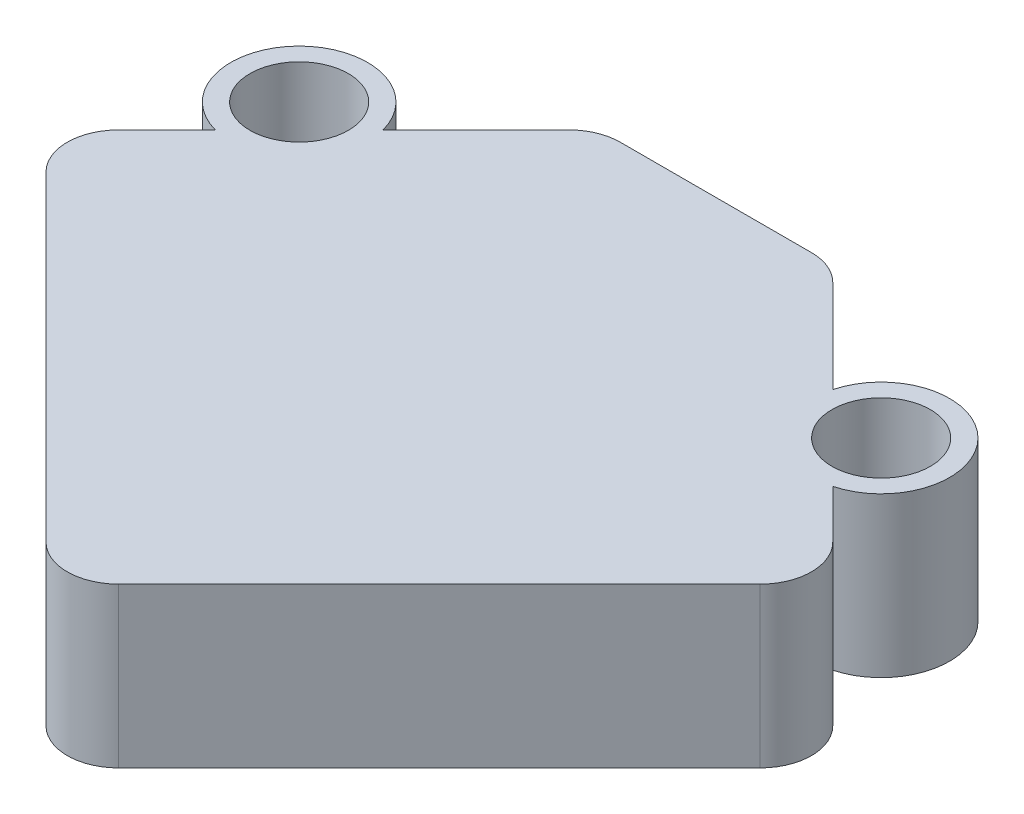
SolidWorks part; units mm, degrees
ref_plane "Front Plane" through (0, 0, 0) normal (0, 0, 1) x (1, 0, 0)
ref_plane "Top Plane" through (0, 0, 0) normal (0, 1, 0) x (1, 0, 0)
ref_plane "Right Plane" through (0, 0, 0) normal (1, 0, 0) x (0, 0, -1)
sketch "Sketch1" plane through (0, 0, 0) normal (0, 1, 0) x (1, 0, 0)
  line L0 (-38.2767, 0) -> (40.0394, 0) construction
  line L1 (0, 59.0518) -> (0, -52.7563) construction
  line L2 (0, 0) -> (52.4416, -52.4416) construction
  line L3 (-20.1525, 0) -> (0, -20.1525)
  line L4 (-20.1525, 0) -> (0, 20.1525)
  line L5 (0, -20.1525) -> (20.1525, 0)
  line L6 (0, 20.1525) -> (20.1525, 0)
  line L7 (-20.1525, 0) -> (20.1525, 0) construction
  line L8 (0, -20.1525) -> (0, 20.1525) construction
  line L9 (-22.981, 0) -> (0, -22.981)
  line L10 (0, -22.981) -> (22.981, 0)
  line L11 (0, 31.4663) -> (-27.2236, 4.2426)
  line L12 (-22.981, 0) -> (-27.2236, 4.2426)
  line L13 (0, 31.4663) -> (27.2236, 4.2426)
  line L14 (22.981, 0) -> (27.2236, 4.2426)
  line L15 (-22.981, 0) -> (0, 22.981)
  line L16 (0, 22.981) -> (22.981, 0)
  line L17 (-17, 8.8094) -> (2.8284, 28.6378) construction
  line L18 (-13.6118, 17.8544) -> (-7.955, 12.1976) construction
  line L19 (-10.7834, 15.026) -> (2.8284, 28.6378) construction
  circle A0 centre (-17, 8.8094) radius 1.75
  circle A1 centre (17, 8.8094) radius 1.75
  circle A2 centre (-17, 8.8094) radius 4
  circle A3 centre (17, 8.8094) radius 4
  point P8 (0, 0)
  dimension "D5" = 3.5
  dimension "D1" = 45
  dimension "D2" = 28.5
  dimension "D3" = 2
  dimension "D4" = 8
  dimension "D6" = 34
extrude "Boss-Extrude1" add sketch "Sketch1" along normal blind 7 contours L16 A3 L6 L5 L3 L4 A2 L15 L9 L10 | L6 A3 L16 L15 A2 L4 | A3 L16 A1 | L15 A2 A0 | A2 L15 | A3 L16 region at (-10.4604, 0, 10.4604) region at (-13.2739, 0, -7.266) region at (-15.0059, 0, -6.8153) region at (-20.7563, 0, -7.8029) region at (15.0059, 0, -6.8153) region at (15.9935, 0, -12.5657)
sketch "Sketch2" plane through (0, 7, 0) normal (0, 1, 0) x (1, 0, 0)
  circle A0 centre (-17, 8.8094) radius 2.875
  circle A1 centre (17, 8.8094) radius 2.875
  dimension "D1" = 5.75
extrude "Cut-Extrude1" cut sketch "Sketch2" against normal offset from surface (5 mm away) 2 up to face at (0, 0, -4.7583)
sketch "Sketch4" plane through (0, 7, 0) normal (0, 1, 0) x (1, 0, 0)
  line L0 (-22.981, 0) -> (22.981, 0) construction
  line L1 (-4, 16.1525) -> (4, 16.1525) construction
  line L2 (-20.1525, 0) -> (0, 20.1525) construction
  line L3 (0, 20.1525) -> (20.1525, 0) construction
  line L4 (-13.1363, 9.8447) -> (0, 22.981) construction
  line L5 (-6.8284, 16.1525) -> (6.8284, 16.1525)
  line L6 (-6.8284, 16.1525) -> (-6.8284, 22.981)
  line L7 (-6.8284, 22.981) -> (6.8284, 22.981)
  line L8 (6.8284, 16.1525) -> (6.8284, 22.981)
  line L9 (0, 22.981) -> (13.1363, 9.8447) construction
  dimension "D1" = 8
extrude "Cut-Extrude3" cut sketch "Sketch4" against normal up to next
sketch "Sketch5" plane through (0, 7, 0) normal (0, 1, 0) x (1, 0, 0)
  line L0 (-4, 16.1525) -> (4, 16.1525)
  line L12 (6.8284, 16.1525) -> (4, 16.1525)
  line L13 (4, 16.1525) -> (20.1525, 0)
  line L14 (20.1525, 0) -> (0, -20.1525)
  line L15 (0, -20.1525) -> (-20.1525, 0)
  line L16 (-20.1525, 0) -> (-4, 16.1525)
  line L17 (-4, 16.1525) -> (-6.8284, 16.1525)
  line L18 (-6.8284, 16.1525) -> (-13.1363, 9.8447)
  line L19 (-18.0353, 4.9457) -> (-22.981, 0)
  line L20 (-22.981, 0) -> (0, -22.981)
  line L21 (0, -22.981) -> (22.981, 0)
  line L22 (22.981, 0) -> (18.0353, 4.9457)
  line L23 (13.1363, 9.8447) -> (6.8284, 16.1525)
  line L24 (6.8284, 16.1525) -> (4, 16.1525)
  line L25 (4, 16.1525) -> (20.1525, 0)
  line L26 (20.1525, 0) -> (0, -20.1525)
  line L27 (0, -20.1525) -> (-20.1525, 0)
  line L28 (-20.1525, 0) -> (-4, 16.1525)
  line L29 (-4, 16.1525) -> (-6.8284, 16.1525)
  line L30 (-6.8284, 16.1525) -> (-13.1363, 9.8447)
  line L31 (-18.0353, 4.9457) -> (-22.981, 0)
  line L32 (-22.981, 0) -> (0, -22.981)
  line L33 (0, -22.981) -> (22.981, 0)
  line L34 (22.981, 0) -> (18.0353, 4.9457)
  line L35 (13.1363, 9.8447) -> (6.8284, 16.1525)
  circle A0 centre (-17, 8.8094) radius 2.875
  circle A1 centre (-17, 8.8094) radius 2.875 construction
  arc A2 (-13.1363, 9.8447) -> (-18.0353, 4.9457) centre (-17, 8.8094) ccw
  arc A3 (18.0353, 4.9457) -> (13.1363, 9.8447) centre (17, 8.8094) ccw
  arc A4 (-13.1363, 9.8447) -> (-18.0353, 4.9457) centre (-17, 8.8094) ccw
  arc A5 (18.0353, 4.9457) -> (13.1363, 9.8447) centre (17, 8.8094) ccw
  circle A6 centre (17, 8.8094) radius 2.875
  circle A7 centre (17, 8.8094) radius 2.875 construction
  line M15 (6.8284, 16.1525) -> (4, 16.1525)
  line M16 (4, 16.1525) -> (20.1525, 0)
  line M17 (20.1525, 0) -> (0, -20.1525)
  line M18 (0, -20.1525) -> (-20.1525, 0)
  line M19 (-20.1525, 0) -> (-4, 16.1525)
  line M20 (-4, 16.1525) -> (-6.8284, 16.1525)
  line M21 (-6.8284, 16.1525) -> (-13.1363, 9.8447)
  arc M22 (-13.1363, 9.8447) -> (-18.0353, 4.9457) centre (-17, 8.8094) ccw
  line M23 (-18.0353, 4.9457) -> (-22.981, 0)
  line M24 (-22.981, 0) -> (0, -22.981)
  line M25 (0, -22.981) -> (22.981, 0)
  line M26 (22.981, 0) -> (18.0353, 4.9457)
  arc M27 (18.0353, 4.9457) -> (13.1363, 9.8447) centre (17, 8.8094) ccw
  line M28 (13.1363, 9.8447) -> (6.8284, 16.1525)
  circle M29 centre (17, 8.8094) radius 2.875
  circle M30 centre (-17, 8.8094) radius 2.875
  dimension "D1" = 0
extrude "Boss-Extrude2" add sketch "Sketch5" along normal blind 0.8 contours M28 M15 M16 M17 M18 M19 M20 M21 M22 M23 M24 M25 M26 M27 M29 M30 | L0 M19 M18 M17 M16 region at (0, 7, 0.3514) region at (-12.5031, 7, -8.5031)
fillet "Fillet1" radius 3 5 edges at (-6.8284, 3.9, -16.1525) (6.8284, 3.9, -16.1525) (22.981, 3.9, 0) (-22.981, 3.9, 0) (0, 3.9, 22.981)
sketch "Sketch6" plane through (0, 0, 0) normal (0, -1, 0) x (1, 0, 0)
  line L0 (-5.2071, -15.6525) -> (-20.8597, 0)
  line L1 (-20.8597, 0) -> (0, 20.8597)
  line L2 (0, 20.8597) -> (20.8597, 0)
  line L3 (20.8597, 0) -> (5.2071, -15.6525)
  line L4 (5.2071, -15.6525) -> (5.5858, -15.6525)
  line L5 (7.3536, -14.9203) -> (13.5002, -8.7737)
  line L6 (16.9643, -5.3096) -> (20.5061, -1.7678)
  line L7 (20.5061, 1.7678) -> (1.7678, 20.5061)
  line L8 (-1.7678, 20.5061) -> (-20.5061, 1.7678)
  line L9 (-20.5061, -1.7678) -> (-16.9643, -5.3096)
  line L10 (-13.5002, -8.7737) -> (-7.3536, -14.9203)
  line L11 (-5.5858, -15.6525) -> (-5.2071, -15.6525)
  line L12 (-13.1363, -9.8447) -> (-7.7071, -15.2739)
  line L13 (-5.5858, -16.1525) -> (-4, -16.1525)
  line L14 (-4, -16.1525) -> (-20.1525, 0)
  line L15 (-20.1525, 0) -> (0, 20.1525)
  line L16 (0, 20.1525) -> (20.1525, 0)
  line L17 (20.1525, 0) -> (4, -16.1525)
  line L18 (4, -16.1525) -> (5.5858, -16.1525)
  line L19 (7.7071, -15.2739) -> (13.1363, -9.8447)
  line L20 (18.0353, -4.9457) -> (20.8597, -2.1213)
  line L21 (20.8597, 2.1213) -> (2.1213, 20.8597)
  line L22 (-2.1213, 20.8597) -> (-20.8597, 2.1213)
  line L23 (-20.8597, -2.1213) -> (-18.0353, -4.9457)
  line L24 (-13.1363, -9.8447) -> (-7.7071, -15.2739)
  line L25 (-5.5858, -16.1525) -> (-4, -16.1525)
  line L26 (-4, -16.1525) -> (-20.1525, 0)
  line L27 (-20.1525, 0) -> (0, 20.1525)
  line L28 (0, 20.1525) -> (20.1525, 0)
  line L29 (20.1525, 0) -> (4, -16.1525)
  line L30 (4, -16.1525) -> (5.5858, -16.1525)
  line L31 (7.7071, -15.2739) -> (13.1363, -9.8447)
  line L32 (18.0353, -4.9457) -> (20.8597, -2.1213)
  line L33 (20.8597, 2.1213) -> (2.1213, 20.8597)
  line L34 (-2.1213, 20.8597) -> (-20.8597, 2.1213)
  line L35 (-20.8597, -2.1213) -> (-18.0353, -4.9457)
  line L36 (-5.2071, -15.6525) -> (-4.7071, -16.1525)
  line L37 (5.2071, -15.6525) -> (4.7071, -16.1525)
  arc A0 (5.5858, -15.6525) -> (7.3536, -14.9203) centre (5.5858, -13.1525) ccw
  arc A1 (13.5002, -8.7737) -> (16.9643, -5.3096) centre (17, -8.8094) ccw
  arc A2 (20.5061, -1.7678) -> (20.5061, 1.7678) centre (18.7383, 0) ccw
  arc A3 (1.7678, 20.5061) -> (-1.7678, 20.5061) centre (0, 18.7383) ccw
  arc A4 (-20.5061, 1.7678) -> (-20.5061, -1.7678) centre (-18.7383, 0) ccw
  arc A5 (-16.9643, -5.3096) -> (-13.5002, -8.7737) centre (-17, -8.8094) ccw
  arc A6 (-7.3536, -14.9203) -> (-5.5858, -15.6525) centre (-5.5858, -13.1525) ccw
  arc A7 (-7.7071, -15.2739) -> (-5.5858, -16.1525) centre (-5.5858, -13.1525) ccw
  arc A8 (5.5858, -16.1525) -> (7.7071, -15.2739) centre (5.5858, -13.1525) ccw
  arc A9 (13.1363, -9.8447) -> (18.0353, -4.9457) centre (17, -8.8094) ccw
  arc A10 (20.8597, -2.1213) -> (20.8597, 2.1213) centre (18.7383, 0) ccw
  arc A11 (2.1213, 20.8597) -> (-2.1213, 20.8597) centre (0, 18.7383) ccw
  arc A12 (-20.8597, 2.1213) -> (-20.8597, -2.1213) centre (-18.7383, 0) ccw
  arc A13 (-18.0353, -4.9457) -> (-13.1363, -9.8447) centre (-17, -8.8094) ccw
  arc A14 (-7.7071, -15.2739) -> (-5.5858, -16.1525) centre (-5.5858, -13.1525) ccw
  arc A15 (5.5858, -16.1525) -> (7.7071, -15.2739) centre (5.5858, -13.1525) ccw
  arc A16 (13.1363, -9.8447) -> (18.0353, -4.9457) centre (17, -8.8094) ccw
  arc A17 (20.8597, -2.1213) -> (20.8597, 2.1213) centre (18.7383, 0) ccw
  arc A18 (2.1213, 20.8597) -> (-2.1213, 20.8597) centre (0, 18.7383) ccw
  arc A19 (-20.8597, 2.1213) -> (-20.8597, -2.1213) centre (-18.7383, 0) ccw
  arc A20 (-18.0353, -4.9457) -> (-13.1363, -9.8447) centre (-17, -8.8094) ccw
  line M20 (-13.1363, -9.8447) -> (-7.7071, -15.2739)
  arc M21 (-7.7071, -15.2739) -> (-5.5858, -16.1525) centre (-5.5858, -13.1525) ccw
  line M22 (-5.5858, -16.1525) -> (-4, -16.1525)
  arc M28 (5.5858, -16.1525) -> (7.7071, -15.2739) centre (5.5858, -13.1525) ccw
  line M29 (7.7071, -15.2739) -> (13.1363, -9.8447)
  arc M30 (13.1363, -9.8447) -> (18.0353, -4.9457) centre (17, -8.8094) ccw
  line M31 (18.0353, -4.9457) -> (20.8597, -2.1213)
  arc M32 (20.8597, -2.1213) -> (20.8597, 2.1213) centre (18.7383, 0) ccw
  line M33 (20.8597, 2.1213) -> (2.1213, 20.8597)
  arc M34 (2.1213, 20.8597) -> (-2.1213, 20.8597) centre (0, 18.7383) ccw
  line M35 (-2.1213, 20.8597) -> (-20.8597, 2.1213)
  arc M36 (-20.8597, 2.1213) -> (-20.8597, -2.1213) centre (-18.7383, 0) ccw
  line M37 (-20.8597, -2.1213) -> (-18.0353, -4.9457)
  arc M38 (-18.0353, -4.9457) -> (-13.1363, -9.8447) centre (-17, -8.8094) ccw
  circle M39 centre (17, -8.8094) radius 1.75
  circle M40 centre (-17, -8.8094) radius 1.75
  dimension "D1" = 0
  dimension "D2" = 0.5
extrude "Boss-Extrude3" add sketch "Sketch6" along normal blind 1.5 contours A6 L10 A5 L9 A4 L8 A3 L7 A2 L6 A1 L5 A0 L4 L37 L30 L36 L11 M28 M29 M30 M31 M32 M33 M34 M35 M36 M37 M38 M20 M21 M22 | L10 A6 L11 L0 L1 L2 L3 L4 A0 L5 A1 L6 A2 L7 A3 L8 A4 L9 A5 M39 M40 region at (-5.3964, 0, -15.5963) region at (-4.9979, 0, -15.9433)
